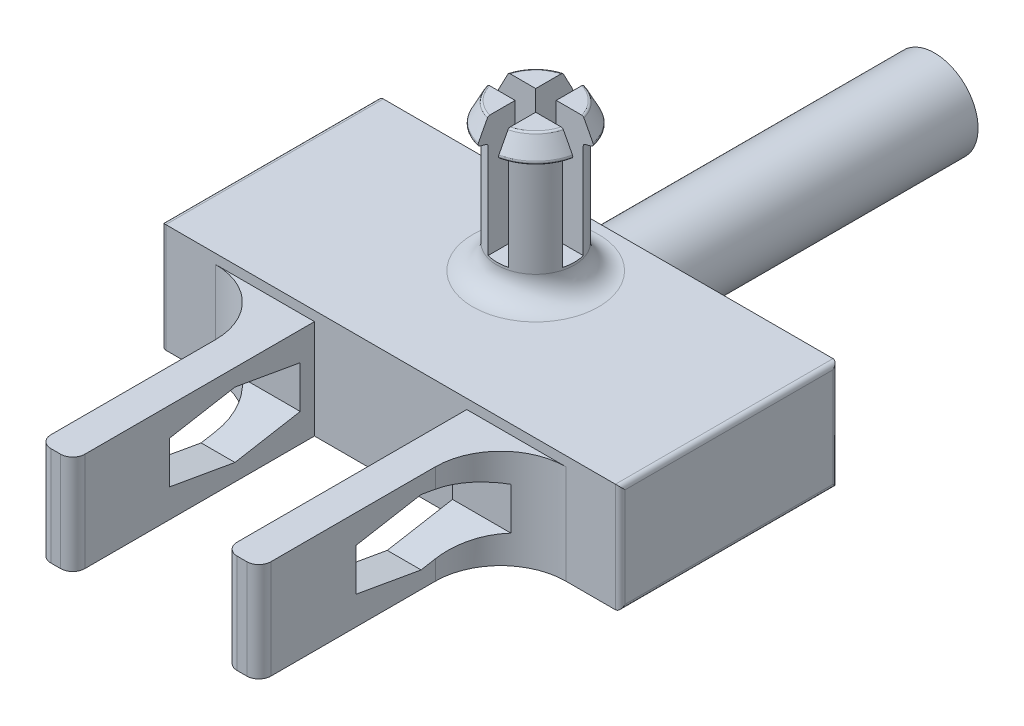
SolidWorks part; units mm, degrees
ref_plane "Front Plane" through (0, 0, 0) normal (0, 0, 1) x (1, 0, 0)
ref_plane "Top Plane" through (0, 0, 0) normal (0, 1, 0) x (1, 0, 0)
ref_plane "Right Plane" through (0, 0, 0) normal (1, 0, 0) x (0, 0, -1)
sketch "Szkic1" plane through (0, 0, 0) normal (0, 1, 0) x (1, 0, 0)
  line L0 (0, -13.1707) -> (0, 4.5) construction
  line L1 (4.55, -4.5) -> (-4.55, -4.5)
  line L2 (9.5, -4.5) -> (9.5, 4.5)
  line L3 (9.5, 4.5) -> (-9.5, 4.5)
  line L4 (-9.5, -4.5) -> (-9.5, 4.5)
  line L5 (9.5, -4.5) -> (-9.5, 4.5) construction
  line L6 (9.5, 4.5) -> (-9.5, -4.5) construction
  line L7 (-9.5, -4.5) -> (-4.55, -4.5)
  line L10 (2.5793, 4.5) -> (-2.5793, 4.5)
  line L13 (-4.55, -4.5) -> (-7.25, -4.5)
  line L14 (-4.55, -4.5) -> (-3.15, -4.5)
  line L15 (-4.55, -4.5) -> (-4.55, -14.5)
  line L16 (-4.55, -14.5) -> (-3.15, -14.5)
  line L17 (-3.15, -4.5) -> (-3.15, -14.5)
  line L18 (4.55, -4.5) -> (3.15, -4.5)
  line L19 (4.55, -4.5) -> (4.55, -14.5)
  line L20 (4.55, -14.5) -> (3.15, -14.5)
  line L21 (3.15, -4.5) -> (3.15, -14.5)
  line L22 (4.55, -4.5) -> (9.5, -4.5)
  line L23 (-4.55, -4.5) -> (-4.55, -7.2)
  line L26 (4.55, -4.5) -> (7.25, -4.5)
  line L27 (4.55, -4.5) -> (4.55, -7.2)
  arc A0 (-4.55, -7.2) -> (-7.25, -4.5) centre (-7.25, -7.2) ccw
  arc A1 (7.25, -4.5) -> (4.55, -7.2) centre (7.25, -7.2) ccw
  point P0 (0, 0)
  dimension "D1" = 9
  dimension "D2" = 19
  dimension "D3" = 10
  dimension "D4" = 1.4
  dimension "D5" = 6.3
  dimension "D6" = 2.7
extrude "Dodanie-wyciągnięcie1" add sketch "Szkic1" along normal blind 4.5 contours L1 L22 L2 L3 L4 L7 region at (0, 0, 0)
extrude "Dodanie-wyciągnięcie2" add sketch "Szkic1<7>" along normal blind 4.1 contours A0 L15 L7 | L17 L1 L15 L16 | A1 L22 L19 | L1 L21 L20 L19 region at (3.85, 0, 9.5) region at (5.1531, 0, 5.1031) region at (-3.85, 0, 9.5) region at (-5.1531, 0, 5.1031)
sketch "Szkic1<7>" plane through (0, 0, 0) normal (0, 1, 0) x (1, 0, 0) same geometry as "Szkic1"
ref_plane "Płaszczyzna1" through (0, 0, -4.5) normal (0, 0, -1) x (-1, 0, 0)
sketch "Szkic2" plane through (0, 0, -4.5) normal (0, 0, -1) x (-1, 0, 0)
  line L0 (0, 0) -> (0, 4.5) construction
  line L1 (-9.5, 4.5) -> (9.5, 4.5) construction
  circle A0 centre (0, 2.25) radius 1.8
  point P5 (0, 2.25)
  dimension "D1" = 3.6
extrude "Dodanie-wyciągnięcie3" add sketch "Szkic2" along normal blind 13.5
ref_plane "Płaszczyzna2" through (-3.15, 0, 0) normal (1, 0, 0) x (0, 0, -1)
sketch "Szkic3" plane through (-3.15, 0, 0) normal (1, 0, 0) x (0, 0, -1)
  line L0 (-7.79, 3.4) -> (-10.49, 2.9239)
  line L1 (-10.49, 2.9239) -> (-10.49, 1.1761)
  line L2 (-10.49, 1.1761) -> (-7.79, 0.7)
  line L3 (-7.79, 0.7) -> (-5.09, 1.1761)
  line L4 (-5.09, 1.1761) -> (-5.09, 2.9239)
  line L5 (-5.09, 2.9239) -> (-7.79, 3.4)
  line L7 (-4.5, 4.1) -> (-14.5, 4.1) construction
  line L8 (-4.5, 0) -> (-14.5, 0) construction
  dimension "D1" = 0.7
  dimension "D2" = 0.7
  dimension "D3" = 100
  dimension "D4" = 100
  dimension "D5" = 5.4
extrude "Wytnij-wyciągnięcie2" cut sketch "Szkic3" along normal through all both and the other way through all
fillet "Zaokrąglenie1" radius 0.5 4 edges at (3.15, 2.05, 14.5) (4.55, 2.05, 14.5) (-4.55, 2.05, 14.5) (-3.15, 2.05, 14.5)
fillet "Zaokrąglenie2" radius 0.2 8 edges at (-9.5, 2.25, -4.5) (-9.5, 4.5, 0) (9.5, 0, 0) (-9.5, 2.25, 4.5) (9.5, 2.25, 4.5) (9.5, 2.25, -4.5) (9.5, 4.5, 0) (-9.5, 0, 0)
ref_plane "Płaszczyzna3" through (0, 4.5, 0) normal (0, 1, 0) x (1, 0, 0)
sketch "Szkic4" plane through (0, 4.5, 0) normal (0, 1, 0) x (1, 0, 0)
  line L0 (-9.3, 1.5) -> (9.3, 1.5) construction
  line L1 (2.475, 4.5) -> (-2.475, 4.5) construction
  line L3 (-9.3, 4.5) -> (-9.3, -4.5) construction
  line L4 (9.3, -4.5) -> (9.3, 4.5) construction
  circle A0 centre (0, 1.5) radius 1.6
  point P6 (0, 1.5)
  dimension "D1" = 3.2
  dimension "D2" = 3
extrude "Dodanie-wyciągnięcie4" add sketch "Szkic4" along normal blind 5.1
ref_plane "Płaszczyzna4" through (0, 9.6, 0) normal (0, 1, 0) x (1, 0, 0)
sketch "Szkic5" plane through (0, 9.6, 0) normal (0, 1, 0) x (1, 0, 0)
  line L0 (0, 3.1) -> (0, -0.1) construction
  circle A0 centre (0, 1.5) radius 1.6 construction
  circle A1 centre (0, 1.5) radius 1.6
  point P5 (0, 1.5)
  dimension "D1" = 3.2
extrude "Dodanie-wyciągnięcie5" add sketch "Szkic5" along normal blind 1
fillet "Zaokrąglenie4" radius 1 1 edges at (0, 4.5, 0.1)
ref_axis "Oś1" through (0, 9.6, -1.5) along (0, -1, 0)
ref_point "Punkt1"
ref_point "Punkt2"
ref_plane "Płaszczyzna5" through (0, 0, 0) normal (1, 0, 0) x (0, 0, -1)
ref_plane "Płaszczyzna Dolnia" through (0, 0, 0) normal (0, -1, 0) x (-1, 0, 0)
ref_plane "Płaszczyzna6" through (0, 10.5, 0) normal (0, 1, 0) x (1, 0, 0)
sketch "Szkic7" plane through (0, 0, 0) normal (1, 0, 0) x (0, 0, -1)
  line L6 (3.1, 10.6) -> (3.1, 9.6)
  line L9 (3.1, 9.6) -> (3.55, 9.7206)
  line L10 (3.55, 9.7206) -> (3.1, 10.6)
  line L13 (1.5, 9.6) -> (1.5, 5.5) construction
  line L16 (4.95, 4.5) -> (-4.95, 4.5) construction
  point P2 (0, 0)
  point P6 (3.1, 9.6)
  dimension "D1" = 2.05
  dimension "D2" = 75
  dimension "D4" = 5.1
revolve "Obrót1" add sketch "Szkic7" angle 360 about axis through (0, 9.6, -1.5) along (0, -1, 0)
fillet "Zaokrąglenie5" radius 0.1 3 edges at (0, 9.6, 0.1) (0, 9.7206, 0.55) (0, 10.6, 0.1)
ref_plane "Płaszczyzna7" through (0, 10.6, 0) normal (0, 1, 0) x (1, 0, 0)
sketch "Szkic6" plane through (0, 10.6, 0) normal (0, 1, 0) x (1, 0, 0)
  line L0 (0.425, 4.7145) -> (0.425, 1.925)
  line L1 (-0.425, 4.7145) -> (-0.425, 1.925)
  line L2 (3.2145, 1.925) -> (0.425, 1.925)
  line L3 (3.2145, 1.075) -> (0.425, 1.075)
  line L4 (-0.425, 1.075) -> (-3.2145, 1.075)
  line L5 (-0.425, 1.925) -> (-3.2145, 1.925)
  line L6 (0.425, 1.075) -> (0.425, -1.7145)
  line L7 (-0.425, 1.075) -> (-0.425, -1.7145)
  line L8 (-0.425, 1.925) -> (0.425, 1.075) construction
  arc A4 (0.425, 4.7145) -> (-0.425, 4.7145) centre (0, 1.5) ccw
  arc A5 (3.2145, 1.075) -> (3.2145, 1.925) centre (0, 1.5) ccw
  arc A6 (-0.425, -1.7145) -> (0.425, -1.7145) centre (0, 1.5) ccw
  arc A7 (-3.2145, 1.925) -> (-3.2145, 1.075) centre (0, 1.5) ccw
  point P18 (0, 1.5)
  dimension "D1" = 0.85
  dimension "D2" = 0.85
extrude "Wytnij-wyciągnięcie3" cut sketch "Szkic6" against normal blind 5
